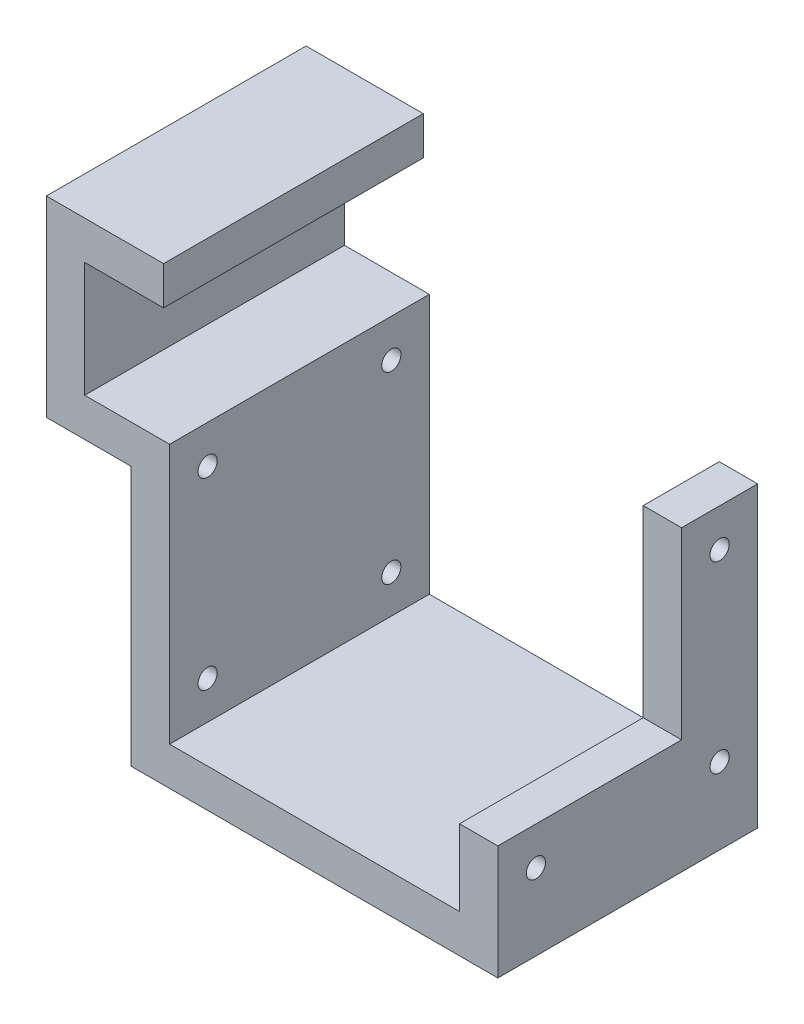
SolidWorks part; units mm, degrees
ref_plane "Front Plane" through (0, 0, 0) normal (0, 0, 1) x (1, 0, 0)
ref_plane "Top Plane" through (0, 0, 0) normal (0, 1, 0) x (1, 0, 0)
ref_plane "Right Plane" through (0, 0, 0) normal (1, 0, 0) x (0, 0, -1)
sketch "Sketch1" plane through (0, 0, 0) normal (0, 0, 1) x (1, 0, 0)
  line L0 (-6.35, -27.85) -> (-6.35, 15.15)
  line L1 (-6.35, 15.15) -> (-20.4, 15.15)
  line L2 (-20.4, 15.15) -> (-20.4, 46.9)
  line L3 (-20.4, 46.9) -> (-1, 46.9)
  line L4 (-1, 46.9) -> (-1, 40.55)
  line L5 (-1, 40.55) -> (-14.05, 40.55)
  line L6 (-14.05, 40.55) -> (-14.05, 21.5)
  line L7 (-14.05, 21.5) -> (0, 21.5)
  line L8 (0, 21.5) -> (0, -21.5)
  line L9 (0, -21.5) -> (48, -21.5)
  line L12 (48, -21.5) -> (48, -27.85)
  line L13 (48, -27.85) -> (-6.35, -27.85)
  line L14 (-14.05, 40.55) -> (24.05, 40.55) construction
  line L15 (-14.05, 40.55) -> (-20.4, 46.9) construction
  line L16 (-14.05, 21.5) -> (-20.4, 15.15) construction
  line L17 (-6.35, 15.15) -> (0, 21.5) construction
  line L18 (0, -21.5) -> (-6.35, -27.85) construction
  line L20 (-14.05, 21.5) -> (-14.05, 40.55) construction
  line L21 (-14.05, 21.5) -> (290.75, 21.5) construction
  line L23 (48, -21.5) -> (0, -21.5) construction
  line L25 (-1, 43.09) -> (-1, 48.9) construction
  dimension "D1" = 6.35
extrude "Boss-Extrude1" add sketch "Sketch1" against normal up to surface (43 mm away) contours L6 L7 L8 L9 L12 L13 L0 L1 L2 L3 L4 L5
sketch "Sketch2" plane through (48, 0, 0) normal (1, 0, 0) x (0, 0, -1)
  line L0 (43, -27.85) -> (0, -27.85) construction
  line L1 (30.4117, -27.85) -> (43, -27.85)
  line L2 (30.4117, -27.85) -> (30.4117, 21.5)
  line L3 (30.4117, 21.5) -> (43, 21.5)
  line L4 (43, -27.85) -> (43, 21.5)
  line L5 (30.4117, -27.85) -> (43, 21.5) construction
  line L6 (30.4117, 21.5) -> (43, -27.85) construction
  line L7 (43, 21.5) -> (0, 21.5) construction
  line L9 (0, -27.85) -> (30.4117, -27.85)
  line L10 (0, -27.85) -> (0, -8.9117)
  line L11 (0, -8.9117) -> (30.4117, -8.9117)
  line L12 (30.4117, -27.85) -> (30.4117, -8.9117)
  line L13 (0, -27.85) -> (30.4117, -8.9117) construction
  line L14 (0, -8.9117) -> (30.4117, -27.85) construction
  line L15 (6.2942, -21.5) -> (6.2942, -8.9117) construction
  line L16 (43, -21.5) -> (0, -21.5) construction
  line L18 (30.4117, -15.2058) -> (43, -15.2058) construction
  circle A2 centre (6.2942, -15.2058) radius 1.5
  circle A3 centre (36.7058, -15.2058) radius 1.5
  circle A4 centre (36.7058, 15.2058) radius 1.5
  circle A5 centre (6.2942, -15.2058) radius 1.5 construction
  point P4 (36.7058, -3.175)
  point P9 (0, 0)
  point P17 (15.2058, -18.3808)
  point P29 (6.2942, -15.2058)
  point P31 (0, 0)
  point P35 (36.7058, -15.2058)
  line M5 (0, -27.85) -> (43, -27.85)
  line M6 (43, -27.85) -> (43, -21.5)
  line M7 (43, -21.5) -> (0, -21.5)
  line M8 (0, -21.5) -> (0, -27.85)
extrude "Boss-Extrude2" add sketch "Sketch2" along normal blind 6.35 contours L2 M5 M7 M8 | L11 L10 L2 A2 M7 | L2 M5 M6 M7 | L4 L3 L2 A4 A3 M7 region at (48, -24.675, -36.7058) region at (48, -24.675, -15.2058) region at (48, -15.2058, -15.3735) region at (48, 0, -36.7058)
sketch "Sketch3" plane through (-6.35, 0, 0) normal (1, 0, 0) x (0, 0, -1)
  line L0 (0, 15.2058) -> (6.2942, 15.2058) construction
  line L1 (0, 21.5) -> (0, -21.5) construction
  circle A0 centre (6.2942, -15.2058) radius 1.5875
  circle A1 centre (6.2942, 15.2058) radius 1.5875
  circle A8 centre (36.7058, 15.2058) radius 1.5875
  circle A9 centre (36.7058, -15.2058) radius 1.5875
  dimension "D1" = 3.175
extrude "Cut-Extrude1" cut sketch "Sketch3" against normal through all both and the other way through all
